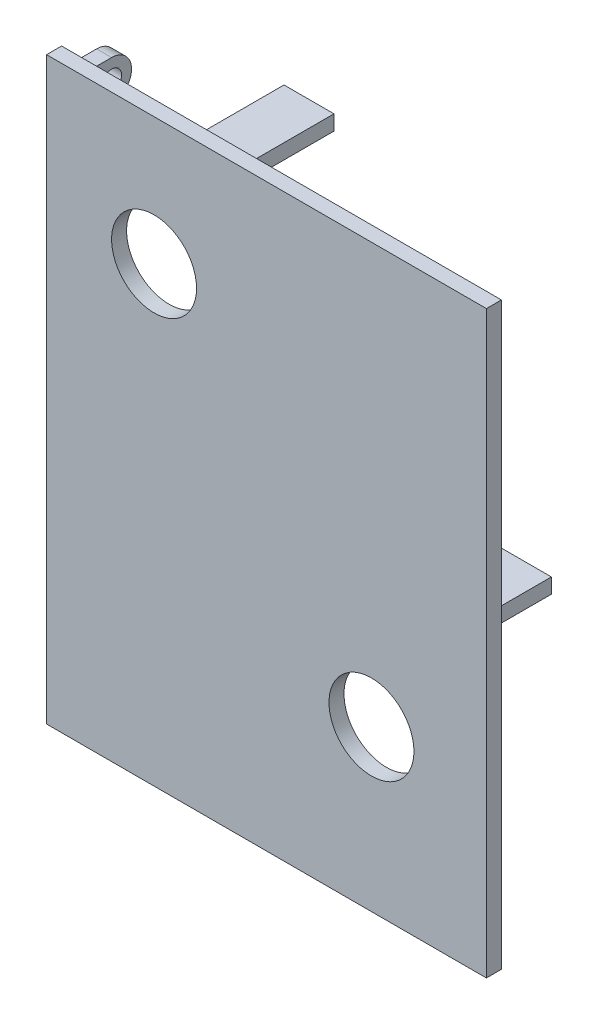
SolidWorks part; units mm, degrees
ref_plane "Front Plane" through (0, 0, 0) normal (0, 0, 1) x (1, 0, 0)
ref_plane "Top Plane" through (0, 0, 0) normal (0, 1, 0) x (1, 0, 0)
ref_plane "Right Plane" through (0, 0, 0) normal (1, 0, 0) x (0, 0, -1)
sketch "Sketch1" plane through (0, 0, 0) normal (0, 0, 1) x (1, 0, 0)
  line L1 (-44, -58) -> (44, -58)
  line L2 (-44, -58) -> (-44, 58)
  line L3 (-44, 58) -> (44, 58)
  line L4 (44, -58) -> (44, 58)
  line L5 (-44, -58) -> (44, 58) construction
  line L6 (-44, 58) -> (44, -58) construction
  circle A0 centre (-22.8181, 25.0296) radius 20 construction
  circle A1 centre (24.0245, 19.8034) radius 20 construction
  point P0 (0, 0)
  dimension "D3" = 40
  dimension "D1" = 88
  dimension "D2" = 116
extrude "Boss-Extrude1" add sketch "Sketch1" along normal blind 3 contours L3 L4 L1 L2
sketch "Sketch2" plane through (0, 0, 3) normal (0, 0, 1) x (1, 0, 0)
  line L0 (-44, -58) -> (-44, 58) construction
  line L1 (-44, 58) -> (44, 58) construction
  line L2 (44, 0) -> (-44, 0) construction
  line L3 (44, -58) -> (44, 58) construction
  line L4 (-44, -58) -> (44, -58) construction
  circle A0 centre (-22.5, 32.5) radius 20 construction
  circle A1 centre (21, -26) radius 20 construction
  circle A2 centre (-22.5, 32.5) radius 8.5
  circle A3 centre (21, -26) radius 8.5
  dimension "D2" = 40
  dimension "D6" = 17
  dimension "D4" = 26
  dimension "D5" = 32.5
  dimension "D3" = 23
  dimension "D1" = 43.5
  dimension "D7" = 25.5
  dimension "D8" = 32
extrude "Cut-Extrude1" cut sketch "Sketch2" against normal through all
sketch "Sketch4" plane through (-44, 0, 0) normal (-1, 0, 0) x (0, 0, 1)
  line L0 (0, 0) -> (10.9251, 0) construction
  line L1 (0, 58) -> (0, 50) construction
  line L2 (0, -58) -> (0, 58) construction
  line L3 (0, 50) -> (-7, 50) construction
  line L4 (-7, 54) -> (0, 54)
  line L5 (0, 54) -> (0, 46)
  line L6 (0, 46) -> (-7, 46)
  line L7 (0, -50) -> (-7, -50) construction
  line L8 (0, -58) -> (0, -50) construction
  line L9 (0, -46) -> (-7, -46)
  line L10 (0, -54) -> (0, -46)
  line L11 (-7, -54) -> (0, -54)
  circle A0 centre (-7, 50) radius 2
  arc A1 (-7, 54) -> (-7, 46) centre (-7, 50) ccw
  arc A2 (-7, -54) -> (-7, -46) centre (-7, -50) cw
  circle A3 centre (-7, -50) radius 2
  dimension "D3" = 8
  dimension "D4" = 4
  dimension "D1" = 7
  dimension "D2" = 8
extrude "Boss-Extrude3" add sketch "Sketch4" against normal blind 3
sketch "Sketch5" plane through (0, 0, 0) normal (0, 0, -1) x (-1, 0, 0)
  line L0 (22.5, 32.5) -> (22.5, 45.5) construction
  line L1 (17.5, 45.5) -> (27.5, 45.5)
  line L2 (27.5, 45.5) -> (27.5, 42.5)
  line L3 (27.5, 42.5) -> (17.5, 42.5)
  line L4 (17.5, 45.5) -> (17.5, 42.5)
  line L5 (-21, -26) -> (-21, -13) construction
  line L6 (-16, -13) -> (-26, -13)
  line L7 (-26, -13) -> (-26, -16)
  line L8 (-26, -16) -> (-16, -16)
  line L9 (-16, -13) -> (-16, -16)
  circle A0 centre (22.5, 32.5) radius 10 construction
  circle A1 centre (22.5, 32.5) radius 13 construction
  circle A2 centre (-21, -26) radius 10 construction
  circle A3 centre (-21, -26) radius 13 construction
  point P9 (22.5, 42.5)
  point P20 (-21, -16)
  dimension "D1" = 20
  dimension "D2" = 3
  dimension "D4" = 3
  dimension "D5" = 20
  dimension "D3" = 5
  dimension "D6" = 5
extrude "Boss-Extrude4" add sketch "Sketch5" along normal blind 28 contours A1 A0 | L1 L4 L3 L2 | L9 L6 L7 L8 region at (-22.5, 44, 0) region at (21, -14.5, 0)
equation "\"mini-flipper-shaft-diameter\"= 26mm"
equation "\"mini-shaft-ring-groove-diam\"= 7.8mm"
equation "\"mini-shaft-ring-groove-width\"= 1mm"
equation "\"dtCoverPlate-DistFrom-GearCent\" = 73mm"
equation "\"wormGearShaft-L\" = \"dtCoverPlate-DistFrom-GearCent\" - 27.75 + 3.75"
equation "\"wormGearShaft-Dsmall\" = 6mm"
equation "\"wormGearShaft-Dworm\" = 12mm"
equation "\"wormL-D\" = 12mm"
equation "\"wormR-D\" = 15mm"
equation "\"wormGearL-D\" = 40mm"
equation "\"wormGearR-D\" = 50mm"
equation "\"D5@Sketch2\"=\"wormGearR-D\"/2 + \"wormR-D\"/2"
equation "\"D4@Sketch2\"=\"wormGearL-D\"/2 + \"wormL-D\"/2"
